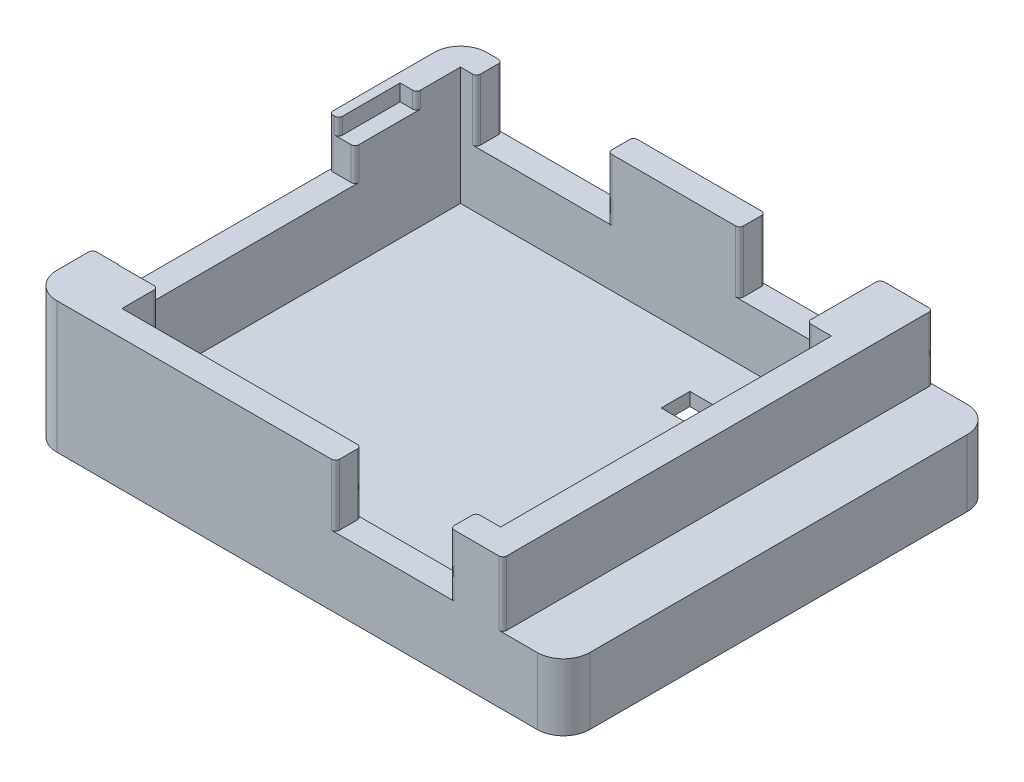
SolidWorks part; units mm, degrees
ref_plane "Front Plane" through (0, 0, 0) normal (0, 0, 1) x (1, 0, 0)
ref_plane "Top Plane" through (0, 0, 0) normal (0, 1, 0) x (1, 0, 0)
ref_plane "Right Plane" through (0, 0, 0) normal (1, 0, 0) x (0, 0, -1)
sketch "Sketch1" plane through (0, 0, 0) normal (0, 1, 0) x (1, 0, 0)
  line L1 (0, 0) -> (103.124, 0)
  line L2 (0, 0) -> (0, 83.185)
  line L3 (0, 83.185) -> (103.124, 83.185)
  line L4 (103.124, 0) -> (103.124, 83.185)
  dimension "D1" = 103.124
  dimension "D2" = 83.185
extrude "Boss-Extrude1" add sketch "Sketch1" along normal blind 25.4
sketch "Sketch2" plane through (0, 25.4, 0) normal (0, 1, 0) x (1, 0, 0)
  line L0 (0, 83.185) -> (0, 0) construction
  line L1 (4.9911, 78.1939) -> (81.1911, 78.1939)
  line L2 (4.9911, 78.1939) -> (4.9911, 11.9253)
  line L3 (12.7, 4.9911) -> (85.9536, 4.9911)
  line L4 (85.9536, 69.0118) -> (85.9536, 4.9911)
  line L5 (103.124, 83.185) -> (0, 83.185) construction
  line L6 (0, 0) -> (103.124, 0) construction
  line L7 (4.9911, 11.9253) -> (12.7, 11.9253)
  line L8 (12.7, 11.9253) -> (12.7, 4.9911)
  line L9 (81.1911, 78.1939) -> (81.1911, 69.0118)
  line L10 (81.1911, 69.0118) -> (85.9536, 69.0118)
  dimension "D1" = 4.9911
  dimension "D2" = 4.9911
  dimension "D3" = 80.9625
  dimension "D4" = 4.9911
  dimension "D5" = 11.9253
  dimension "D6" = 12.7
  dimension "D7" = 76.2
  dimension "D8" = 14.1732
extrude "Cut-Extrude1" cut sketch "Sketch2" against normal blind 22.86
sketch "Sketch3" plane through (0, 25.4, 0) normal (0, 1, 0) x (1, 0, 0)
  line L0 (0, 0) -> (103.124, 0) construction
  line L1 (103.124, 83.185) -> (91.3765, 83.185)
  line L2 (103.124, 83.185) -> (103.124, 0)
  line L3 (103.124, 0) -> (91.3765, 0)
  line L4 (91.3765, 83.185) -> (91.3765, 0)
  dimension "D1" = 11.7475
extrude "Cut-Extrude2" cut sketch "Sketch3" against normal blind 12.4841
sketch "Sketch4" plane through (0, 0, -83.185) normal (0, 0, -1) x (-1, 0, 0)
  line L0 (-91.3765, 25.4) -> (0, 25.4) construction
  line L1 (-81.2165, 25.4) -> (-58.9915, 25.4)
  line L2 (-81.2165, 25.4) -> (-81.2165, 13.4937)
  line L3 (-81.2165, 13.4937) -> (-58.9915, 13.4937)
  line L4 (-58.9915, 25.4) -> (-58.9915, 13.4937)
  line L5 (-91.3765, 12.9159) -> (-91.3765, 25.4) construction
  dimension "D1" = 10.16
  dimension "D2" = 22.225
  dimension "D3" = 11.9062
extrude "Cut-Extrude3" cut sketch "Sketch4" against normal blind 127
sketch "Sketch5" plane through (0, 0, -83.185) normal (0, 0, -1) x (-1, 0, 0)
  line L0 (-58.9915, 25.4) -> (0, 25.4) construction
  line L1 (-8.1026, 25.4) -> (-33.5026, 25.4)
  line L2 (-8.1026, 25.4) -> (-8.1026, 13.4938)
  line L3 (-8.1026, 13.4938) -> (-33.5026, 13.4937)
  line L4 (-33.5026, 25.4) -> (-33.5026, 13.4937)
  line L5 (0, 25.4) -> (0, 0) construction
  dimension "D1" = 25.4
  dimension "D2" = 8.1026
  dimension "D3" = 11.9062
extrude "Cut-Extrude4" cut sketch "Sketch5" against normal blind 5.08
sketch "Sketch6" plane through (0, 0, 0) normal (-1, 0, 0) x (0, 0, 1)
  line L0 (-83.185, 25.4) -> (0, 25.4) construction
  line L1 (-12.0015, 25.4) -> (-57.785, 25.4)
  line L2 (-12.0015, 25.4) -> (-12.0015, 15.875)
  line L3 (-12.0015, 15.875) -> (-57.785, 15.875)
  line L4 (-57.785, 25.4) -> (-57.785, 15.875)
  line L5 (-83.185, 25.4) -> (-83.185, 0) construction
  dimension "D1" = 45.7835
  dimension "D2" = 9.525
  dimension "D3" = 25.4
extrude "Cut-Extrude5" cut sketch "Sketch6" against normal blind 5.08
sketch "Sketch7" plane through (0, 25.4, 0) normal (0, 1, 0) x (1, 0, 0)
  line L1 (4.9911, 57.785) -> (1.8161, 57.785)
  line L2 (4.9911, 57.785) -> (4.9911, 69.6912)
  line L3 (4.9911, 69.6912) -> (1.8161, 69.6912)
  line L4 (1.8161, 57.785) -> (1.8161, 69.6912)
  dimension "D1" = 11.9062
  dimension "D2" = 3.175
extrude "Cut-Extrude6" cut sketch "Sketch7" against normal blind 3.175
sketch "Sketch8" plane through (0, 0, 0) normal (0, -1, 0) x (1, 0, 0)
  line L1 (58.674, -63.3413) -> (69.7865, -63.3413)
  line L2 (58.674, -63.3413) -> (58.674, -68.8975)
  line L3 (58.674, -68.8975) -> (69.7865, -68.8975)
  line L4 (69.7865, -63.3413) -> (69.7865, -68.8975)
  line L6 (103.124, -83.185) -> (0, -83.185) construction
  line L8 (103.124, 0) -> (103.124, -83.185) construction
  dimension "D1" = 33.3375
  dimension "D2" = 5.5562
  dimension "D3" = 14.2875
  dimension "D4" = 11.1125
extrude "Cut-Extrude7" cut sketch "Sketch8" against normal blind 5.08
fillet "Fillet1" radius 5.08 4 edges at (103.124, 6.4579, -83.185) (103.124, 6.4579, 0) (0, 12.7, 0) (0, 12.7, -83.185)
fillet "Fillet2" radius 0.762 20 edges at (91.3765, 19.1579, 0) (81.2165, 19.4469, 0) (81.2165, 19.4469, -4.9911) (58.9915, 19.4469, 0) (58.9915, 19.4469, -4.9911) (12.7, 13.97, -11.9253) (0, 20.6375, -12.0015) (0, 20.6375, -57.785) (91.3765, 19.1579, -83.185) (81.2165, 19.4469, -69.0118) (81.2165, 19.4469, -83.185) (58.9915, 19.4469, -83.185) (58.9915, 19.4469, -78.1939) (33.5026, 19.4469, -78.1939) (33.5026, 19.4469, -83.185) (8.1026, 19.4469, -83.185) (8.1026, 19.4469, -78.1939) (1.8161, 23.8125, -57.785) (4.9911, 23.8125, -69.6912) (4.9911, 19.05, -57.785)
